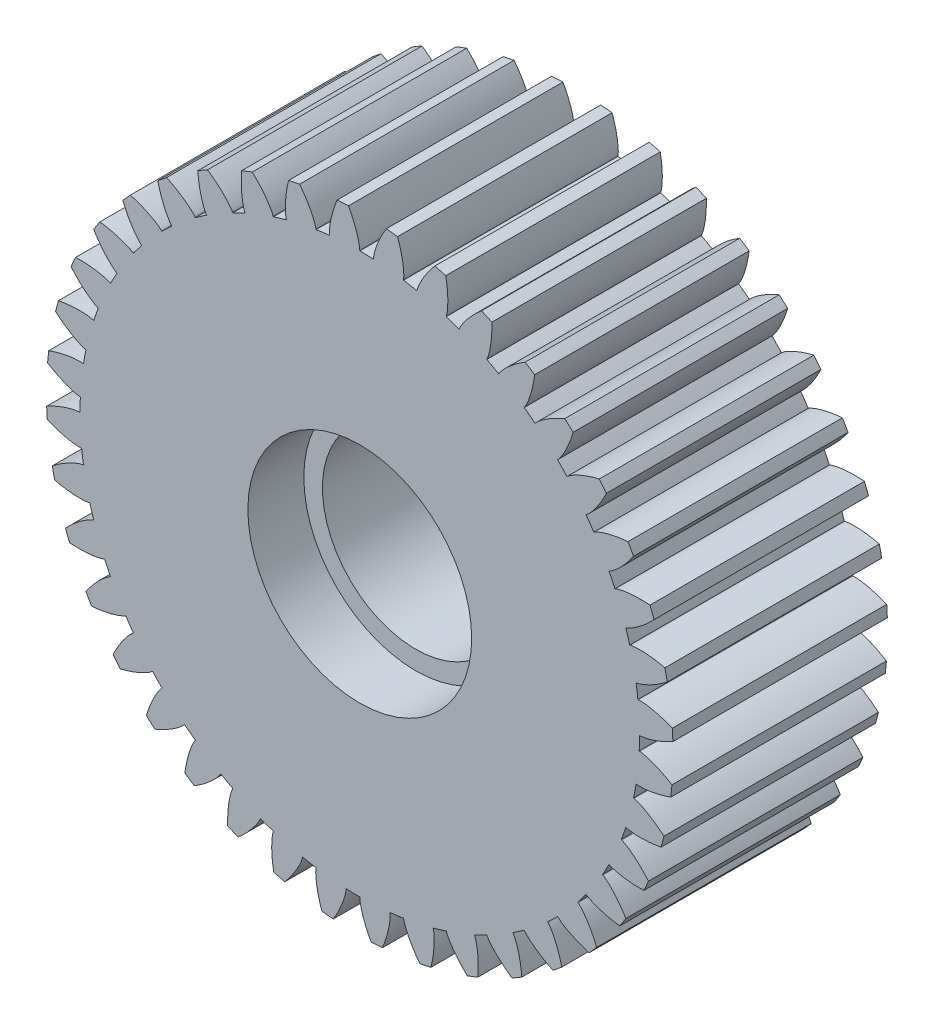
SolidWorks part; units mm, degrees
ref_plane "Front Plane" through (0, 0, 0) normal (0, 0, 1) x (1, 0, 0)
ref_plane "Top Plane" through (0, 0, 0) normal (0, 1, 0) x (1, 0, 0)
ref_plane "Right Plane" through (0, 0, 0) normal (1, 0, 0) x (0, 0, -1)
sketch "Sketch1" plane through (0, 0, 0) normal (0, 0, 1) x (1, 0, 0)
  circle A0 centre (0, 0) radius 16.8
  dimension "D1" = 33.6
extrude "Boss-Extrude1" add sketch "Sketch1" along normal mid plane 11.5
sketch "Sketch2" plane through (0, 0, 0) normal (0, 0, 1) x (1, 0, 0)
  line L0 (0, 0) -> (15.0351, 0) construction
  line L1 (0, 0) -> (15.9953, -0.3898) construction
  line L2 (0, 0) -> (15.0172, -0.7324) construction
  line L3 (15.0351, 0) -> (15, 0)
  line L4 (15.0172, -0.7324) -> (14.9822, -0.7307)
  circle A0 centre (0, 0) radius 16 construction
  circle A1 centre (0, 0) radius 15.0351 construction
  circle A2 centre (0, 0) radius 15
  circle A3 centre (0, 0) radius 16.8 construction
  circle A4 centre (0, 0) radius 16.8
  spline S0 degree 4 poles (15.0351, 0) (15.0402, 0.0001) (15.0546, 0.0005) (15.0819, 0.0022) (15.1262, 0.0063) (15.1827, 0.0135) (15.2554, 0.0248) (15.3409, 0.041) (15.4344, 0.0616) (15.5358, 0.0872) (15.6366, 0.1155) (15.7366, 0.1462) (15.8359, 0.1791) (15.9556, 0.2217) (16.0984, 0.2765) (16.2641, 0.346) (16.4505, 0.4312) (16.6387, 0.5248) (16.8223, 0.6224) (17.006, 0.7273) (17.1823, 0.8333) (17.3632, 0.9498) (17.5292, 1.0605) (17.7127, 1.1916) (17.86, 1.2993) (18.0514, 1.4488) (18.1637, 1.5393) (18.2939, 1.6477) (18.3513, 1.6972) (18.3866, 1.7276) knots 0 0 0 0 0 0.005377 0.015084 0.028532 0.04661 0.064855 0.092111 0.119476 0.146842 0.174209 0.201575 0.228941 0.256307 0.307035 0.361767 0.4165 0.471232 0.525964 0.580697 0.635429 0.690161 0.744894 0.799626 0.854358 0.909091 0.954545 1 1 1 1 1 construction
  spline S1 degree 4 poles (15.0351, 0) (15.0402, 0.0001) (15.0546, 0.0005) (15.0819, 0.0022) (15.1262, 0.0063) (15.1827, 0.0135) (15.2554, 0.0248) (15.3409, 0.041) (15.4344, 0.0616) (15.5358, 0.0872) (15.6366, 0.1155) (15.7366, 0.1462) (15.8359, 0.1791) (15.9556, 0.2217) (16.0984, 0.2765) (16.2641, 0.346) (16.4505, 0.4312) (16.6387, 0.5248) (16.8223, 0.6224) (17.006, 0.7273) (17.1823, 0.8333) (17.3632, 0.9498) (17.5292, 1.0605) (17.7127, 1.1916) (17.86, 1.2993) (18.0099, 1.4164) (18.0826, 1.4743) (18.1196, 1.5042) knots 0 0 0 0 0 0.005377 0.015084 0.028532 0.04661 0.064855 0.092111 0.119476 0.146842 0.174209 0.201575 0.228941 0.256307 0.307035 0.361767 0.4165 0.471232 0.525964 0.580697 0.635429 0.690161 0.744894 0.799626 0.854358 0.909091 0.909091 0.909091 0.909091 0.909091
  spline S2 degree 4 poles (15.0172, -0.7324) (15.0224, -0.7327) (15.0367, -0.7338) (15.0638, -0.7369) (15.108, -0.7432) (15.164, -0.753) (15.2361, -0.7679) (15.3207, -0.7882) (15.4131, -0.8134) (15.5131, -0.8439) (15.6124, -0.877) (15.7108, -0.9126) (15.8084, -0.9503) (15.9259, -0.9987) (16.0659, -1.0604) (16.228, -1.1379) (16.41, -1.232) (16.5934, -1.3347) (16.772, -1.4411) (16.9503, -1.5549) (17.1213, -1.6693) (17.2964, -1.7944) (17.4568, -1.9131) (17.6336, -2.053) (17.7755, -2.1678) (17.9594, -2.3264) (18.0671, -2.4223) (18.192, -2.5369) (18.2468, -2.5891) (18.2806, -2.6212) knots 0 0 0 0 0 0.005377 0.015084 0.028532 0.04661 0.064855 0.092111 0.119476 0.146842 0.174209 0.201575 0.228941 0.256307 0.307035 0.361767 0.4165 0.471232 0.525964 0.580697 0.635429 0.690161 0.744894 0.799626 0.854358 0.909091 0.954545 1 1 1 1 1 construction
  spline S3 degree 4 poles (15.0172, -0.7324) (15.0224, -0.7327) (15.0367, -0.7338) (15.0638, -0.7369) (15.108, -0.7432) (15.164, -0.753) (15.2361, -0.7679) (15.3207, -0.7882) (15.4131, -0.8134) (15.5131, -0.8439) (15.6124, -0.877) (15.7108, -0.9126) (15.8084, -0.9503) (15.9259, -0.9987) (16.0659, -1.0604) (16.228, -1.1379) (16.41, -1.232) (16.5934, -1.3347) (16.772, -1.4411) (16.9503, -1.5549) (17.1213, -1.6693) (17.2964, -1.7944) (17.4568, -1.9131) (17.6336, -2.053) (17.7755, -2.1678) (17.9196, -2.292) (17.9893, -2.3533) (18.0248, -2.385) knots 0 0 0 0 0 0.005377 0.015084 0.028532 0.04661 0.064855 0.092111 0.119476 0.146842 0.174209 0.201575 0.228941 0.256307 0.307035 0.361767 0.4165 0.471232 0.525964 0.580697 0.635429 0.690161 0.744894 0.799626 0.854358 0.909091 0.909091 0.909091 0.909091 0.909091
  dimension "D1" = 32
  dimension "D2" = 30.0702
  dimension "D3" = 30
  dimension "D4" = 1.396
  dimension "D5" = 1.396
extrude "Cut-Extrude1" cut sketch "Sketch2" against normal through all both and the other way through all contours A2 S3 A4 S1 region at (16.0514, -0.3912, 0)
pattern_circular "CirPattern2" count 40 over 360 about axis through (0, 0, 5.75) along (0, 0, -1) of "Cut-Extrude1"
sketch "Sketch3" plane through (0, 0, 5.75) normal (0, 0, 1) x (1, 0, 0)
  circle A0 centre (0, 0) radius 6
  dimension "D1" = 12
extrude "Cut-Extrude2" cut sketch "Sketch3" against normal blind 3
sketch "Sketch4" plane through (0, 0, 2.75) normal (0, 0, 1) x (1, 0, 0)
  circle A0 centre (0, 0) radius 5
  dimension "D1" = 10
extrude "Cut-Extrude3" cut sketch "Sketch4" against normal through all
mirror "Mirror1" about plane through (0, 0, 0) normal (0, 0, 1) of "Cut-Extrude2"
equation "\"Np\"= 40"
equation "\"module\"= 0.8"
equation "\"pressure angle\"= 20deg"
equation "\"h_a\"= 1 * \"module\"'addendum"
equation "\"h_b\"= 1.25 * \"module\"'dedendum"
equation "\"clr_tip_root\"= \"h_f\" - \"h_a\"'clearance of gear tooth tip and root"
equation "\"dp_p\"= \"module\" * \"Np\"'PCD"
equation "\"db_p\"= \"dp_p\" * cos ( \"pressure angle\" )'base CD"
equation "\"D1@Sketch1\"= \"dp_p\" + 2*\"h_a\" "
equation "\"fw_p\"= \"fw_r\""
equation "\"D1@Boss-Extrude1\"=\"fw_p\""
equation "\"D1@Sketch2\"=\"dp_p\""
equation "\"D2@Sketch2\"= \"db_p\""
equation "\"D3@Sketch2\"=\"dp_p\"- 2*\"h_b\""
equation "\"alpha_p\"= sqr ( \"dp_p\" ^ 2 - \"db_p\" ^ 2 ) / \"db_p\" * 180 / pi - \"pressure angle\""
equation "\"D4@Sketch2\"= 360 / ( 4 * \"Np\" ) - \"alpha_p\""
equation "\"beta_p\"= ( 360 / ( 4 * \"Np\" ) - \"alpha_p\" ) * 2"
equation "\"D5@Sketch2\"= 360 / ( 4 * \"Np\" ) - \"alpha_p\""
equation "\"D1@CirPattern2\"=\"Np\""
equation "\"Nr\"= \"Ns\" + 2 * \"Np\"'num teeth"
equation "\"pressure_angle\"= 20deg"
equation "\"h_f\"= 1.25 * \"module\"'dedendum"
equation "\"dp_r\"= \"module\" * \"Nr\"'PCD"
equation "\"db_r\"= \"dp_r\" * cos ( \"pressure_angle\" )'base CD"
equation "\"fw_r\"= 11.5mm'face width"
equation "\"alpha_r\"= sqr ( \"dp_r\" ^ 2 - \"db_r\" ^ 2 ) / \"db_r\" * 180 / pi - \"pressure_angle\""
equation "\"beta_r\"= ( 360 / ( 4 * \"Nr\" ) + \"alpha_r\" ) * 2"
equation "\"bearing_ID\"= \"module\" * ( \"Ns\" + \"Np\" ) + 10"
equation "\"bearing_OD\"= 1.18 * \"bearing_ID\" + 8.57"
equation "\"bearing_height\"= 0.09 * \"bearing_ID\" + 4.62"
equation "\"clearance_planet\"=1.5"
equation "\"case_dist\"= \"sec_carrier_thickness\" + \"clearance_planet\" + \"sun_coupler_hub_thickness\" - \"case_mounting_surface_height\""
equation "\"Motor_case_OD_max\"= \"case_mounting_PCD\" + \"case_mounting_hole_allen_socket_dia\" + \"clearance_case_mount_holes_shell_thickness\" * 2"
equation "\"case_mounting_PCD\"= \"motor_case_OD_base\" + \"case_mounting_hole_shift\" * 2"
equation "\"bearing mount thickness\"= IIF((\"bearing_OD\" + \"output_mounting_hole_dia\" * 4) > (\"Nr\" * \"module\" + 2 * \"h_b\"), \"output_mounting_hole_dia\" * 2, ((\"Nr\" * \"module\" + 2 * \"h_b\" - (\"bearing_OD\" + \"output_mounting_hole_dia\" * 4)) / 2) + \"output_mounting_hole_dia\" * 2 + \"standard_clearance_1_5mm\")"
equation "\"case_mounting_hole_dia\"=3"
equation "\"output_mounting_PCD\"= \"bearing_OD\" + \"bearing mount thickness\""
equation "\"output_mounting_hole_dia\"= 4"
equation "\"clearance_case_mount_holes_shell_thickness\"= 1"
equation "\"motor_case_OD_base\"= \"motor_OD\" + \"clearance_motor_and_case\" * 2 + \"Motor_case_thickness\" * 2"
equation "\"sec_carrier_thickness\"= 5"
equation "\"sun_coupler_hub_thickness\"= 4"
equation "\"clearance_sun_coupler_sec_carrier\"= 1.5"
equation "\"clearance_motor_and_case\" = IIF(\"ring_OD\" < \"motor_OD\", 5, (\"ring_OD\" - \"motor_OD\")/2 + 5)"
equation "\"motor_OD\"= 88.6"
equation "\"Motor_case_thickness\"= 2.5"
equation "\"Motor_case_ID\"= \"motor_OD\" + \"clearance_motor_and_case\" * 2"
equation "\"case_mounting_hole_shift\"= \"case_mounting_hole_dia\" / 2 - 0.5"
equation "\"output_mounting_nut_wrench_size\"= 7"
equation "\"output_mounting_nut_thickness\"= 3.2"
equation "\"case_mounting_hole_allen_socket_dia\"= 5.5"
equation "\"output_mounting_nut_depth\"= 3"
equation "\"case_mounting_bolt_depth\"= 4.5"
equation "\"Ns\"= 20"
equation "\"ring_radial_thickness\"= 5"
equation "\"ring_OD\"= \"Nr\" * \"module\" + \"ring_radial_thickness\" * 2"
equation "\"ring_to_chamfer_clearance\"= 2"
equation "\"Motor_case_OD_base_to_chamfer\"=5"
equation "\"pattern_offset_from_motor_case_OD_base\"= 3"
equation "\"pattern_bulge_dia\"= 3"
equation "\"pattern_num_bulge\"= 18"
equation "\"pattern_depth\"= 2"
equation "\"motor_height\"= 43"
equation "\"case_mounting_wrench_size\"= 5.5"
equation "\"case_mounting_nut_clearance\"= 2"
equation "\"base_plate_thickness\"= 4"
equation "\"case_mounting_nut_thickness\"= 2.4"
equation "\"case_mounting_surface_height\"= 4"
equation "\"motor_mount_hole_PCD\"= 32"
equation "\"motor_mount_hole_dia\"= 4"
equation "\"motor_mount_hole_num\"= 4"
equation "\"central_hole_offset_from_motor_mount_PCD\"= 5"
equation "\"wire_slot_dist_from_center\"= 30"
equation "\"wire_slot_length\"= 10"
equation "\"wire_slot_radius\"= 4"
equation "\"driver_upper_holes_dist_from_center\"= 23"
equation "\"driver_lower_holes_dist_from_center\"= 15"
equation "\"driver_side_holes_dist_from_center\"= 20"
equation "\"driver_mount_holes_dia\"= 2.5"
equation "\"driver_mount_inserts_OD\"= 3.5"
equation "\"driver_mount_thickness\"= 1.5"
equation "\"driver_mount_height\"= 4"
equation "\"air_flow_hole_offset\"= 3"
equation "\"num_planet\"= 3"
equation "\"planet_pin_bolt_dia\"= 5"
equation "\"planet_pin_socket_head_dia\"= 8.5"
equation "\"carrier_PCD\"= ( \"Np\" + \"Ns\" ) * \"module\""
equation "\"planet_shaft_dia\"= 8"
equation "\"planet_shaft_step_offset\"= 1"
equation "\"carrier_trapezoidal_support_sun_offset\"= 5"
equation "\"carrier_trapezoidal_support_hole_PCD_offset_bearing_ID\"= 4"
equation "\"carrier_trapezoidal_support_hole_dia\"= 3"
equation "\"carrier_trapezoidal_support_hole_socket_head_dia\"= 5.5"
equation "\"carrier_bearing_step_width\"= 1.5"
equation "\"standard_clearance_1_5mm\"=1.5"
equation "\"standard_fillet_1_5mm\"= 1.5"
equation "\"sun_shaft_bearing_OD\"= 16"
equation "\"sun_shaft_bearing_width\"= 4"
equation "\"standard_bearing_insertion_chamfer\"= 0.5"
equation "\"carrier_trapezoidal_support_hole_wrench_size\"= 5.5"
equation "\"planet_pin_bolt_wrench_size\"= 8"
equation "\"planet_bearing_OD\"= 12"
equation "\"planet_bearing_width\"= 3"
equation "\"planet_bore\"= 10"
equation "\"D1@Cut-Extrude2\"=\"planet_bearing_width\""
equation "\"D1@Sketch3\"=\"planet_bearing_OD\""
equation "\"D1@Sketch4\"=\"planet_bore\""
equation "\"motor_output_hole_PCD\"= 23"
equation "\"motor_output_hole_dia\"= 4"
equation "\"motor_output_hole_num\"= 4"
equation "\"dp_s\"= \"module\" * \"Ns\"'PCD"
equation "\"db_s\"= \"dp_s\" * cos ( \"pressure angle\" )'base CD"
equation "\"fw_s_calc\"= 13mm'face width"
equation "\"alpha_s\"= sqr ( \"dp_s\" ^ 2 - \"db_s\" ^ 2 ) / \"db_s\" * 180 / pi - \"pressure angle\""
equation "\"beta_s\"= ( 360 / ( 4 * \"Ns\" ) - \"alpha_s\" ) * 2"
equation "\"sun_shaft_bearing_ID\"= 8"
equation "\"sun_hub_dia\"= \"motor_output_hole_PCD\" + \"motor_output_hole_dia\" + \"standard_clearance_1_5mm\" * 4"
equation "\"sun_central_bolt_dia\"= 5"
equation "\"sun_central_bolt_socket_head_dia\"= 8.5"
equation "\"fw_s_used\"= \"fw_p\" + \"clearance_planet\" + \"sec_carrier_thickness\" + \"standard_clearance_1_5mm\""
equation "\"motor_output_hole_CSK_OD\"= 9'8.96 is exact value"
equation "\"motor_output_hole_CSK_head_height\"= 2.5"
equation "\"bearing_retainer_thickness\"= 2"
